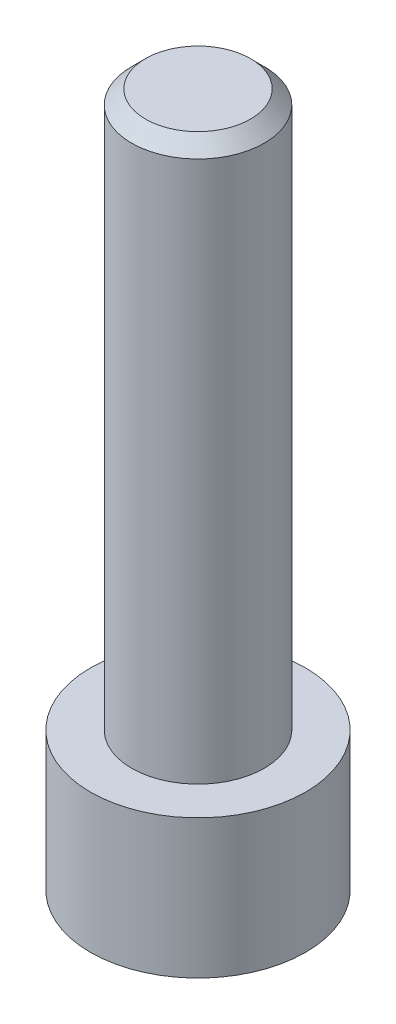
SolidWorks part; units mm, degrees
ref_plane "Front Plane" through (0, 0, 0) normal (0, 0, 1) x (1, 0, 0)
ref_plane "Top Plane" through (0, 0, 0) normal (0, 1, 0) x (1, 0, 0)
ref_plane "Right Plane" through (0, 0, 0) normal (1, 0, 0) x (0, 0, -1)
sketch "Sketch1" plane through (0, 0, 0) normal (0, 1, 0) x (1, 0, 0)
  line L1 (4.4745, 0) -> (2.2372, 3.875) construction
  line L2 (2.2372, 3.875) -> (-2.2372, 3.875) construction
  line L3 (-2.2372, 3.875) -> (-4.4745, 0) construction
  line L4 (-4.4745, 0) -> (-2.2372, -3.875) construction
  line L5 (-2.2372, -3.875) -> (2.2372, -3.875) construction
  line L6 (2.2372, -3.875) -> (4.4745, 0) construction
  circle A0 centre (0, 0) radius 3.875
  dimension "D1" = 7.75
extrude "Boss-Extrude1" add sketch "Sketch1" along normal blind 25
sketch "Sketch2" plane through (0, 25, 0) normal (0, 1, 0) x (1, 0, 0)
  circle A0 centre (0, 0) radius 2.39
  dimension "D1" = 4.78
extrude "Cut-Extrude1" cut sketch "Sketch2" against normal blind 20 flip side to cut
ref_axis "Axis1" through (0, 5, 0) along (0, 1, 0)
chamfer "Chamfer1" distance 0.5 angle 45 1 edges at (0, 25, 2.39)
sketch "Sketch5" plane through (0, 25, 0) normal (0, 1, 0) x (1, 0, 0)
  circle A0 centre (0, 0) radius 2.39
  dimension "D1" = 4.78
curve "Helix/Spiral1" pitch 0.7 height 25 turns 35.7143
ref_plane "Plane1" through (0, 25, 2.39) normal (-0.9989, -0.0466, 0) x (0, 0, 1)
sketch "Sketch8" plane through (0, 0, 0) normal (0, -1, 0) x (1, 0, 0)
  line L1 (2.6443, 0) -> (1.3221, 2.29)
  line L2 (1.3221, 2.29) -> (-1.3221, 2.29)
  line L3 (-1.3221, 2.29) -> (-2.6443, 0)
  line L4 (-2.6443, 0) -> (-1.3221, -2.29)
  line L5 (-1.3221, -2.29) -> (1.3221, -2.29)
  line L6 (1.3221, -2.29) -> (2.6443, 0)
  circle A0 centre (0, 0) radius 2.29 construction
  dimension "D1" = 4.58
extrude "Cut-Extrude2" cut sketch "Sketch8" against normal blind 3.36
